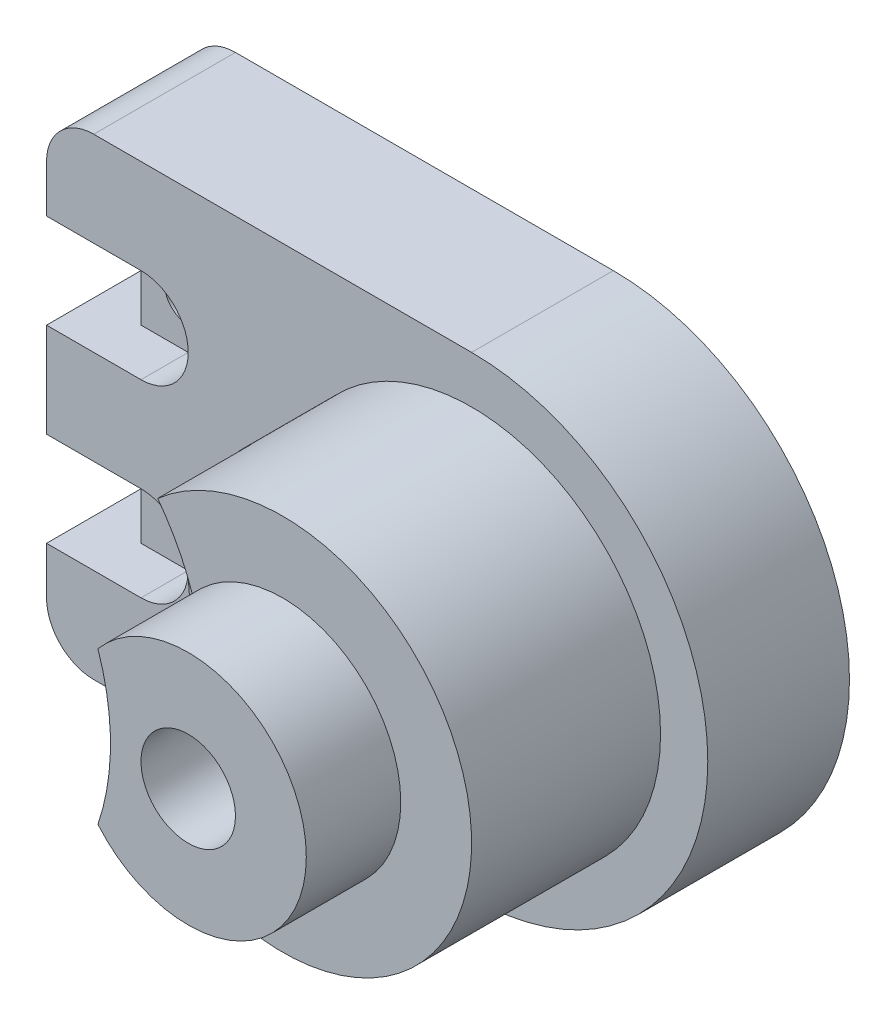
SolidWorks part; units mm, degrees
ref_plane "Front Plane" through (0, 0, 0) normal (0, 0, 1) x (1, 0, 0)
ref_plane "Top Plane" through (0, 0, 0) normal (0, 1, 0) x (1, 0, 0)
ref_plane "Right Plane" through (0, 0, 0) normal (1, 0, 0) x (0, 0, -1)
sketch "Sketch1" plane through (0, 0, 0) normal (0, 0, 1) x (1, 0, 0)
  line L0 (0, 0) -> (0, 100)
  line L1 (0, 100) -> (90, 100)
  line L2 (0, 0) -> (90, 0)
  arc A0 (90, 100) -> (90, 0) centre (90, 50) cw
  dimension "D1" = 50
  dimension "D2" = 100
  dimension "D3" = 90
  dimension "D4" = 90
extrude "Boss-Extrude1" add sketch "Sketch1" along normal blind 30 contours A0 L1 L0 L2 region at (65.1167, 50, 0)
sketch "Sketch2" plane through (0, 0, 30) normal (0, 0, 1) x (1, 0, 0)
  line L0 (0, 0) -> (0, 100) construction
  line L1 (0, 90) -> (0, 100)
  line L2 (0, 100) -> (10, 100)
  line L3 (0, 10) -> (0, 0)
  line L4 (0, 0) -> (10, 0)
  line L6 (0, 80) -> (10, 80)
  line L7 (0, 80) -> (0, 60)
  line L8 (0, 60) -> (10, 60)
  line L9 (10, 80) -> (10, 60)
  line L10 (0, 20) -> (10, 20)
  line L11 (0, 20) -> (0, 40)
  line L12 (0, 40) -> (10, 40)
  line L13 (10, 20) -> (10, 40)
  arc A0 (0, 90) -> (10, 100) centre (10, 90) cw
  arc A1 (0, 10) -> (10, 0) centre (10, 10) ccw
  dimension "D1" = 10
  dimension "D2" = 10
  dimension "D3" = 10
  dimension "D4" = 10
  dimension "D5" = 10
  dimension "D6" = 10
  dimension "D7" = 10
  dimension "D8" = 10
  dimension "D9" = 20
  dimension "D10" = 10
  dimension "D11" = 10
  dimension "D12" = 20
  dimension "D13" = 10
  dimension "D14" = 20
extrude "Cut-Extrude1" cut sketch "Sketch2" against normal blind 30
sketch "Sketch3" plane through (0, 0, 30) normal (0, 0, 1) x (1, 0, 0)
  circle A0 centre (90, 50) radius 40
  dimension "D1" = 80
extrude "Boss-Extrude2" add sketch "Sketch3" along normal blind 40
sketch "Sketch4" plane through (0, 0, 70) normal (0, 0, 1) x (1, 0, 0)
  circle A0 centre (90, 50) radius 25
  dimension "D1" = 50
  dimension "D2" = 50
  dimension "D3" = 0
extrude "Boss-Extrude3" add sketch "Sketch4" along normal blind 20
sketch "Sketch5" plane through (0, 0, 30) normal (0, 0, 1) x (1, 0, 0)
  line L0 (10, 80) -> (20, 80)
  line L1 (10, 60) -> (20, 60)
  line L2 (10, 80) -> (10, 60)
  arc A0 (20, 80) -> (20, 60) centre (20, 70) cw
  line M12 (10, 80) -> (10, 60)
  dimension "D3" = 10
  dimension "D1" = 10
  dimension "D2" = 10
extrude "Cut-Extrude2" cut sketch "Sketch5" against normal blind 42 contours A0 L0 L1 M12 region at (19.0665, 70, 30)
sketch "Sketch6" plane through (0, 0, 30) normal (0, 0, 1) x (1, 0, 0)
  line L0 (10, 40) -> (20, 40)
  line L1 (10, 20) -> (20, 20)
  line L2 (10, 40) -> (10, 20)
  arc A0 (20, 40) -> (20, 20) centre (20, 30) cw
  line M5 (10, 40) -> (10, 20)
  dimension "D3" = 10
  dimension "D1" = 10
  dimension "D2" = 10
extrude "Cut-Extrude3" cut sketch "Sketch6" against normal blind 42 contours A0 L0 L1 M5 region at (19.0665, 30, 30)
ref_plane "Plane1" through (0, 0, 10) normal (0, 0, 1) x (1, 0, 0)
sketch "Sketch7" plane through (0, 0, 10) normal (0, 0, 1) x (1, 0, 0)
  line L0 (10, 80) -> (10, 60)
  line L1 (10, 80) -> (20, 80)
  line L2 (10, 60) -> (20, 60)
  line L3 (0, 40) -> (0, 60) construction
  line L4 (0, 60) -> (20, 60) construction
  arc A0 (20, 80) -> (20, 60) centre (20, 70) cw
  dimension "D4" = 10
  dimension "D1" = 20
  dimension "D2" = 10
  dimension "D3" = 10
  dimension "D5" = 10
  dimension "D6" = 0
extrude "Boss-Extrude4" add sketch "Sketch7" along normal blind 10
sketch "Sketch8" plane through (0, 0, 10) normal (0, 0, 1) x (1, 0, 0)
  line L0 (10, 40) -> (10, 20)
  line L1 (10, 40) -> (20, 40)
  line L2 (10, 20) -> (20, 20)
  line L3 (0, 20) -> (20, 20) construction
  arc A0 (20, 40) -> (20, 20) centre (20, 30) cw
  dimension "D4" = 10
  dimension "D1" = 20
  dimension "D2" = 10
  dimension "D3" = 10
  dimension "D5" = 10
  dimension "D6" = 0
extrude "Boss-Extrude5" add sketch "Sketch8" along normal blind 10
sketch "Sketch9" plane through (0, 0, 20) normal (0, 0, 1) x (1, 0, 0)
  circle A0 centre (20, 70) radius 5
  circle A1 centre (20, 30) radius 5
  dimension "D1" = 10
  dimension "D2" = 10
extrude "Cut-Extrude4" cut sketch "Sketch9" against normal blind 10
sketch "Sketch10" plane through (0, 0, 70) normal (0, 0, 1) x (1, 0, 0)
  line L0 (63.5425, 80) -> (63.5425, 20)
  arc A0 (63.5425, 80) -> (63.5425, 20) centre (23.5425, 50) cw
  circle A1 centre (90, 50) radius 40 construction
  arc A2 (63.5425, 80) -> (63.5425, 20) centre (90, 50) ccw
  circle M1 centre (90, 50) radius 40
  circle M2 centre (90, 50) radius 25
  dimension "D4" = 30
  dimension "D5" = 40
  dimension "D3" = 50
  dimension "D1" = 60
  dimension "D2" = 63.5425
extrude "Cut-Extrude5" cut sketch "Sketch10" against normal blind 20 and the other way blind 20 contours L0 M1 | A0 M2 | A0 L0 M2 region at (67.225, 73.0599, 70) region at (58.0383, 50, 70) region at (69.5609, 50, 70)
sketch "Sketch11" plane through (0, 0, 50) normal (0, 0, 1) x (1, 0, 0)
  line L0 (10, 100) -> (90, 100) construction
  circle A0 centre (60, 50) radius 5
  dimension "D1" = 10
  dimension "D2" = 50
  dimension "D3" = 60
extrude "Cut-Extrude6" cut sketch "Sketch11" against normal blind 50
sketch "Sketch14" plane through (0, 0, 90) normal (0, 0, 1) x (1, 0, 0)
  point P0 (90, 50)
hole_wizard "Ø20.0mm Dowel Hole1" positions "3DSketch2" profile "Sketch15" hole size "Ø20.0" standard "ISO"
sketch3d "3DSketch2"
  point P0 (90, 50, 90)
sketch "Sketch15" plane through (90, 50, 90) normal (1, 0, 0) x (0, -1, 0)
  line L0 (0, 0) -> (0, 36.0086)
  line L1 (0, 36.0086) -> (10, 30)
  line L2 (10, 30) -> (10, 0)
  line L5 (10, 0) -> (0, 0)
  line L10 (0, 36.0086) -> (-10, 30) construction
  line L11 (0, -6.35) -> (0, 107.95) construction
  dimension "Hole Dia." = 20
  dimension "Hole Depth" = 30
  dimension "Drill Angle" = 118
